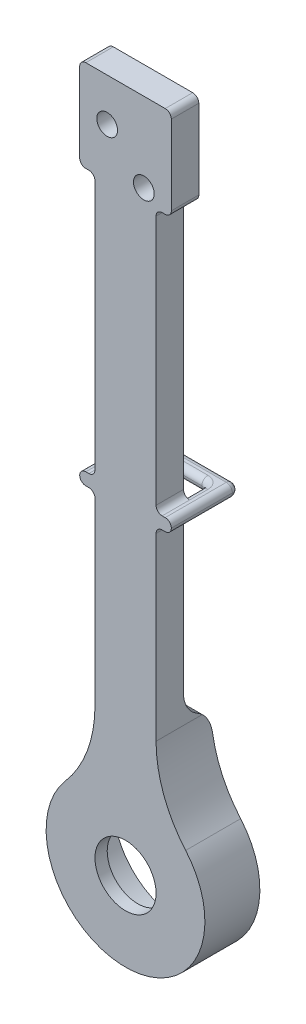
SolidWorks part; units mm, degrees
ref_plane "Front Plane" through (0, 0, 0) normal (0, 0, 1) x (1, 0, 0)
ref_plane "Top Plane" through (0, 0, 0) normal (0, 1, 0) x (1, 0, 0)
ref_plane "Right Plane" through (0, 0, 0) normal (1, 0, 0) x (0, 0, -1)
other "Center of Mass"
sketch "Sketch1" plane through (0, 0, 0) normal (0, 0, 1) x (1, 0, 0)
  line L0 (-5, 12) -> (5, 12)
  line L1 (5, 12) -> (5, 112)
  line L2 (5, 112) -> (-5, 112)
  line L3 (-5, 112) -> (-5, 12)
  line L4 (0, 112) -> (0, 12) construction
  line L6 (-7.5, 112) -> (7.5, 112)
  line L7 (-7.5, 112) -> (-7.5, 97)
  line L8 (-7.5, 97) -> (7.5, 97)
  line L9 (7.5, 112) -> (7.5, 97)
  circle A0 centre (0, 0) radius 5
  circle A1 centre (0, 0) radius 13
  point P14 (0, 97)
  dimension "D1" = 10
  dimension "D2" = 26
  dimension "D3" = 10
  dimension "D4" = 100
  dimension "D5" = 15
  dimension "D6" = 15
extrude "Boss-Extrude1" add sketch "Sketch1" along normal mid plane 9 contours L2 L4 A1 L1 | L0 A1 A0 | L4 L2 L3 A1 | A1 L4 L0 | L4 A1 L0 | L7 L6 L9 L8
sketch "Sketch2" plane through (0, 0, -4.5) normal (0, 0, -1) x (-1, 0, 0)
  circle A0 centre (0, 0) radius 11
  dimension "D1" = 22
extrude "Cut-Extrude1" cut sketch "Sketch2" against normal blind 7
fillet "Fillet7" radius 1 6 edges at (7.5, 112, 0) (-7.5, 112, 0) (-7.5, 97, 0) (7.5, 97, 0) (5, 97, 0) (-5, 97, 0)
fillet "Fillet1" radius 20 2 edges at (5, 12, 0) (-5, 12, 0)
sketch "Sketch3" plane through (0, 0, 0) normal (1, 0, 0) x (0, 0, -1)
  line L0 (-4.5, 21.5407) -> (4.5, 21.5407) construction
  line L3 (0, 21.5407) -> (4.5, 21.5407)
  line L4 (0, 21.5407) -> (0, 112)
  line L5 (0, 112) -> (4.5, 112)
  line L6 (4.5, 21.5407) -> (4.5, 112)
extrude "Cut-Extrude2" cut sketch "Sketch3" against normal through all both and the other way through all
sketch "Sketch4" plane through (0, 0, 4.5) normal (0, 0, 1) x (1, 0, 0)
  line L1 (-5, 96) -> (-5, 21.5407) construction
  line L2 (5, 21.5407) -> (5, 96) construction
  line L3 (-6.5, 112) -> (6.5, 112) construction
  point P0 (-3, 105)
  point P1 (3, 99)
  dimension "D1" = 7
  dimension "D2" = 6
  dimension "D3" = 2
  dimension "D4" = 2
hole_wizard "M3 Clearance Hole1" positions "Sketch5" profile "Sketch6" hole size "M3" standard "ANSI Metric" end condition through all
sketch "Sketch5" plane through (0, 0, 4.5) normal (0, 0, 1) x (1, 0, 0)
  point P0 (3, 99)
  point P3 (-3, 105)
sketch "Sketch6" plane through (3, 99, 4.5) normal (1, 0, 0) x (0, -1, 0)
  line L0 (0, 0) -> (0, 9)
  line L1 (0, 9) -> (1.7, 9)
  line L2 (1.7, 9) -> (1.7, 0)
  line L5 (1.7, 0) -> (0, 0)
  line L11 (0, -6.35) -> (0, 107.95) construction
  dimension "Thru Hole Dia." = 3.4
  dimension "Thru Hole Depth" = 9
fillet "Fillet5" radius 4.5 1 edges at (0, 21.5407, 0)
fillet "Fillet6" radius 4.5 1 edges at (0, 21.5407, -4.5)
ref_plane "Plane1" through (0, -13, 0) normal (0, -1, 0) x (-1, 0, 0)
sketch "Sketch7" [suppressed] plane through (0, 0, 0) normal (0, 0, -1) x (-1, 0, 0)
  point P0 (0, 44)
hole_wizard "M3 Clearance Hole2" [suppressed] positions "Sketch8" profile "Sketch9" hole size "M3" standard "ANSI Metric"
sketch "Sketch8" [suppressed] plane through (0, 0, 0) normal (0, 0, -1) x (-1, 0, 0)
  point P0 (0, 44)
sketch "Sketch9" plane through (0, 44, 0) normal (1, 0, 0) x (0, 1, 0)
  line L0 (0, 0) -> (0, 4.5)
  line L1 (0, 4.5) -> (1.7, 4.5)
  line L2 (1.7, 4.5) -> (1.7, 0)
  line L5 (1.7, 0) -> (0, 0)
  line L11 (0, -6.35) -> (0, 107.95) construction
  dimension "Thru Hole Dia." = 3.4
  dimension "Thru Hole Depth" = 4.5
ref_plane "Plane2" through (0, 52, 0) normal (0, -1, 0) x (-1, 0, 0)
sketch "Sketch10" plane through (0, 52, 0) normal (0, -1, 0) x (-1, 0, 0)
  line L0 (5, -4.5) -> (5, -2.5) construction
  line L1 (7.5, -4.5) -> (-7.5, -4.5)
  line L2 (7.5, -4.5) -> (7.5, 6.5)
  line L3 (7.5, 6.5) -> (-7.5, 6.5)
  line L4 (-7.5, -4.5) -> (-7.5, 6.5)
  line L5 (5, -4.5) -> (-5, -4.5)
  line L6 (5, -4.5) -> (5, 4)
  line L7 (5, 4) -> (-5, 4)
  line L8 (-5, -4.5) -> (-5, 4)
  line L9 (-4.7, -4.5) -> (-1.3, -4.5) construction
  line L10 (5, 0) -> (-5, 0) construction
  point P11 (0, 6.5)
  point P17 (0, 4)
  dimension "D1" = 2.5
  dimension "D2" = 2.5
  dimension "D3" = 8.5
extrude "Boss-Extrude2" add sketch "Sketch10" against normal blind 2 contours L1 L8 L7 L6 L2 L3 L4
fillet "Fillet8" radius 1 12 edges at (5, 54, -2) (5, 52, -2) (-5, 54, -2) (-5, 52, -2) (0, 54, -6.5) (-7.5, 54, -1) (7.5, 54, -1) (7.5, 52, -1) (-7.5, 52, -1) (0, 52, -6.5) (0, 52, -4) (0, 54, -4)
fillet "Fillet9" radius 1 4 edges at (5, 54, 2.25) (-5, 54, 2.25) (-5, 52, 2.25) (5, 52, 2.25)
sketch "Sketch11" plane through (0, 0, 4.5) normal (0, 0, 1) x (1, 0, 0)
  point P0 (0, 0)
